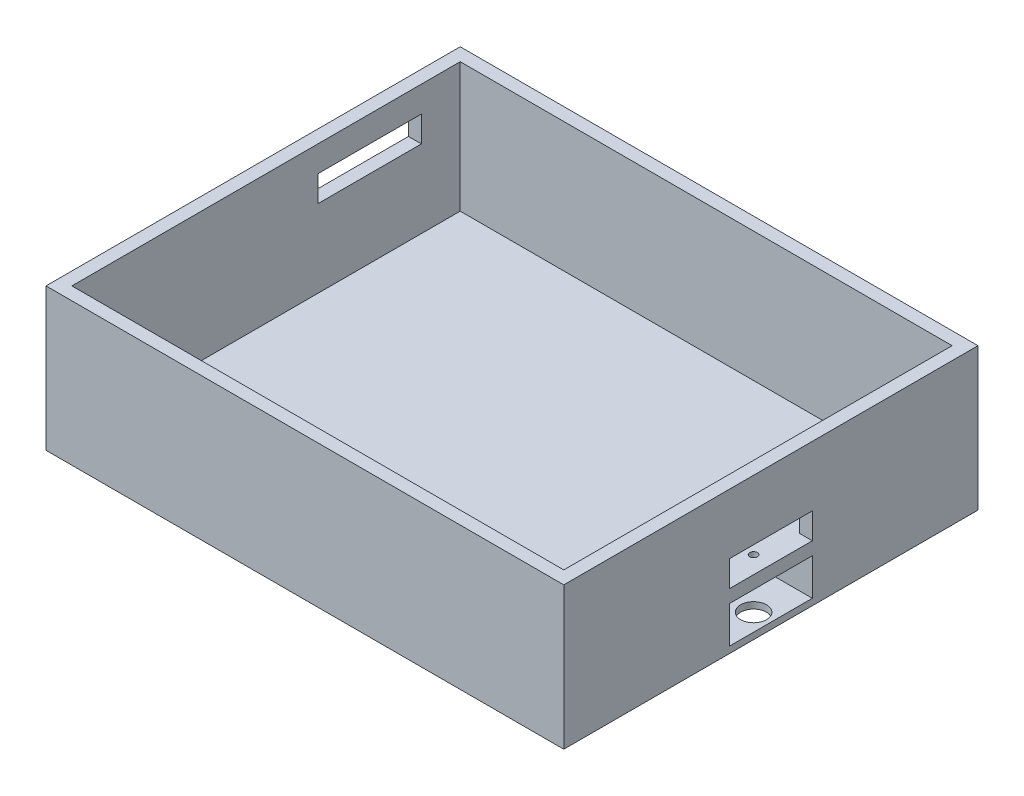
SolidWorks part; units mm, degrees
ref_plane "Front Plane" through (0, 0, 0) normal (0, 0, 1) x (1, 0, 0)
ref_plane "Top Plane" through (0, 0, 0) normal (0, 1, 0) x (1, 0, 0)
ref_plane "Right Plane" through (0, 0, 0) normal (1, 0, 0) x (0, 0, -1)
sketch "Sketch1" plane through (0, 0, 0) normal (0, 1, 0) x (1, 0, 0)
  line L1 (-127, -101.6) -> (127, -101.6)
  line L2 (-127, -101.6) -> (-127, 101.6)
  line L3 (-127, 101.6) -> (127, 101.6)
  line L4 (127, -101.6) -> (127, 101.6)
  line L5 (-127, -101.6) -> (127, 101.6) construction
  line L6 (-127, 101.6) -> (127, -101.6) construction
  point P0 (0, 0)
  dimension "D1" = 254
  dimension "D2" = 203.2
extrude "Boss-Extrude1" add sketch "Sketch1" along normal blind 6.35
sketch "Sketch2" plane through (0, 6.35, 0) normal (0, 1, 0) x (1, 0, 0)
  line L0 (127, -101.6) -> (127, 101.6) construction
  line L1 (-127, 101.6) -> (127, 101.6)
  line L2 (-127, 101.6) -> (-127, 95.25)
  line L3 (-127, 95.25) -> (127, 95.25)
  line L4 (127, 101.6) -> (127, 95.25)
  line L5 (-127, 101.6) -> (-127, -101.6) construction
  line L6 (127, -101.6) -> (-127, -101.6)
  line L7 (127, -101.6) -> (127, -95.25)
  line L8 (127, -95.25) -> (-127, -95.25)
  line L9 (-127, -101.6) -> (-127, -95.25)
  line L11 (-127, -95.25) -> (-120.65, -95.25)
  line L12 (-127, -95.25) -> (-127, 95.25)
  line L13 (-127, 95.25) -> (-120.65, 95.25)
  line L14 (-120.65, -95.25) -> (-120.65, 95.25)
  line L15 (127, 95.25) -> (120.65, 95.25)
  line L16 (127, 95.25) -> (127, -95.25)
  line L17 (127, -95.25) -> (120.65, -95.25)
  line L18 (120.65, 95.25) -> (120.65, -95.25)
  line M13 (127, -101.6) -> (127, 101.6)
  line M14 (127, 101.6) -> (-127, 101.6)
  line M15 (-127, 101.6) -> (-127, -101.6)
  line M16 (-127, -101.6) -> (127, -101.6)
  dimension "D1" = 6.35
extrude "Boss-Extrude2" add sketch "Sketch2" along normal blind 63.5 contours L8 L14 L3 M15 | L3 M15 M13 M14 | L3 L18 L8 M13 | L8 M13 M15 M16 region at (0, 6.35, -98.425) region at (-123.825, 6.35, 0) region at (123.825, 6.35, 0) region at (0, 6.35, 98.425)
sketch "Sketch3" plane through (0, 69.85, 0) normal (0, 1, 0) x (1, 0, 0)
  line L0 (120.65, 95.25) -> (120.65, -95.25) construction
  line L1 (120.65, 20.32) -> (127, 20.32)
  line L2 (120.65, 20.32) -> (120.65, -20.32)
  line L3 (120.65, -20.32) -> (127, -20.32)
  line L4 (127, 20.32) -> (127, -20.32)
  line L5 (127, -101.6) -> (127, 101.6) construction
  point P8 (120.65, 0)
  dimension "D1" = 40.64
extrude "Cut-Extrude1" cut sketch "Sketch3" against normal up to surface (63.5 mm away) up to face at (0, 6.35, 0)
sketch "Sketch4" plane through (0, 6.35, 0) normal (0, 1, 0) x (1, 0, 0)
  line L0 (120.65, -20.32) -> (127, -20.32) construction
  line L1 (127, 20.32) -> (76.2, 20.32)
  line L2 (127, 20.32) -> (127, -20.32)
  line L3 (127, -20.32) -> (76.2, -20.32)
  line L4 (76.2, 20.32) -> (76.2, -20.32)
  dimension "D1" = 50.8
extrude "Cut-Extrude2" cut sketch "Sketch4" against normal blind 3.175
sketch "Sketch5" plane through (0, 6.35, 0) normal (0, 1, 0) x (1, 0, 0)
  line L1 (120.65, 20.32) -> (88.9, 20.32)
  line L2 (120.65, 20.32) -> (120.65, 26.67)
  line L3 (120.65, 26.67) -> (88.9, 26.67)
  line L4 (88.9, 20.32) -> (88.9, 26.67)
  dimension "D1" = 31.75
  dimension "D2" = 6.35
extrude "Boss-Extrude3" add sketch "Sketch5" along normal up to surface (14.913 mm away)
sketch "Sketch6" plane through (0, 21.263, 0) normal (0, 1, 0) x (1, 0, 0)
  line L1 (88.9, 26.67) -> (127, 26.67)
  line L2 (88.9, 26.67) -> (88.9, 0)
  line L3 (88.9, 0) -> (127, 0)
  line L4 (127, 26.67) -> (127, 0)
  line L5 (127, 20.32) -> (127, 101.6) construction
extrude "Boss-Extrude4" add sketch "Sketch6" along normal blind 6.35
mirror "Mirror1" about plane through (0, 0, 0) normal (0, 0, 1) of "Boss-Extrude4", "Boss-Extrude3"
sketch "Sketch7" plane through (0, 27.613, 0) normal (0, 1, 0) x (1, 0, 0)
  circle A0 centre (99.4, 0) radius 1.85 construction
  circle A1 centre (118.5, 0) radius 1.85 construction
  circle A2 centre (99.4, 0) radius 1.85
  circle A3 centre (118.5, 0) radius 1.85
extrude "Cut-Extrude3" cut sketch "Sketch7" against normal up to next
sketch "Sketch8" plane through (0, 69.85, 0) normal (0, 1, 0) x (1, 0, 0)
  line L0 (-127, 101.6) -> (-127, -101.6) construction
  line L1 (-127, 76.2) -> (-120.65, 76.2)
  line L2 (-127, 76.2) -> (-127, 25.4)
  line L3 (-127, 25.4) -> (-120.65, 25.4)
  line L4 (-120.65, 76.2) -> (-120.65, 25.4)
  line L5 (-120.65, -95.25) -> (-120.65, 95.25) construction
  line L6 (127, 101.6) -> (-127, 101.6) construction
  dimension "D1" = 50.8
  dimension "D2" = 25.4
extrude "Cut-Extrude4" cut sketch "Sketch8" against normal blind 25.4
sketch "Sketch9" plane through (0, 0, 0) normal (0, -1, 0) x (1, 0, 0)
  circle A0 centre (99.4, 0) radius 1.85 construction
  circle A1 centre (118.5, 0) radius 1.85 construction
  circle A2 centre (99.4, 0) radius 1.85 construction
  circle A3 centre (118.5, 0) radius 1.85 construction
  circle A4 centre (99.4, 0) radius 6.35
  circle A5 centre (118.5, 0) radius 6.35
  dimension "D1" = 12.7
extrude "Cut-Extrude5" cut sketch "Sketch9" against normal up to next
sketch "Sketch10" plane through (127, 0, 0) normal (1, 0, 0) x (0, 0, -1)
  line L0 (20.32, 27.613) -> (20.32, 69.85) construction
  line L1 (-20.32, 69.85) -> (20.32, 69.85)
  line L2 (-20.32, 69.85) -> (-20.32, 40.313)
  line L3 (-20.32, 40.313) -> (20.32, 40.313)
  line L4 (20.32, 69.85) -> (20.32, 40.313)
  line L5 (-20.32, 27.613) -> (20.32, 27.613) construction
  dimension "D1" = 12.7
extrude "Boss-Extrude5" add sketch "Sketch10" against normal up to surface (6.35 mm away) up to face at (120.65, 34.6043, -47.4133)
sketch "Sketch11" plane through (-127, 0, 0) normal (-1, 0, 0) x (0, 0, 1)
  line L0 (-25.4, 44.45) -> (-25.4, 69.85) construction
  line L1 (-76.2, 69.85) -> (-25.4, 69.85)
  line L2 (-76.2, 69.85) -> (-76.2, 57.15)
  line L3 (-76.2, 57.15) -> (-25.4, 57.15)
  line L4 (-25.4, 69.85) -> (-25.4, 57.15)
  line L6 (-76.2, 44.45) -> (-25.4, 44.45) construction
  dimension "D1" = 12.7
extrude "Boss-Extrude6" add sketch "Sketch11" against normal up to surface (6.35 mm away) up to face at (-120.65, 47.625, -25.4)
